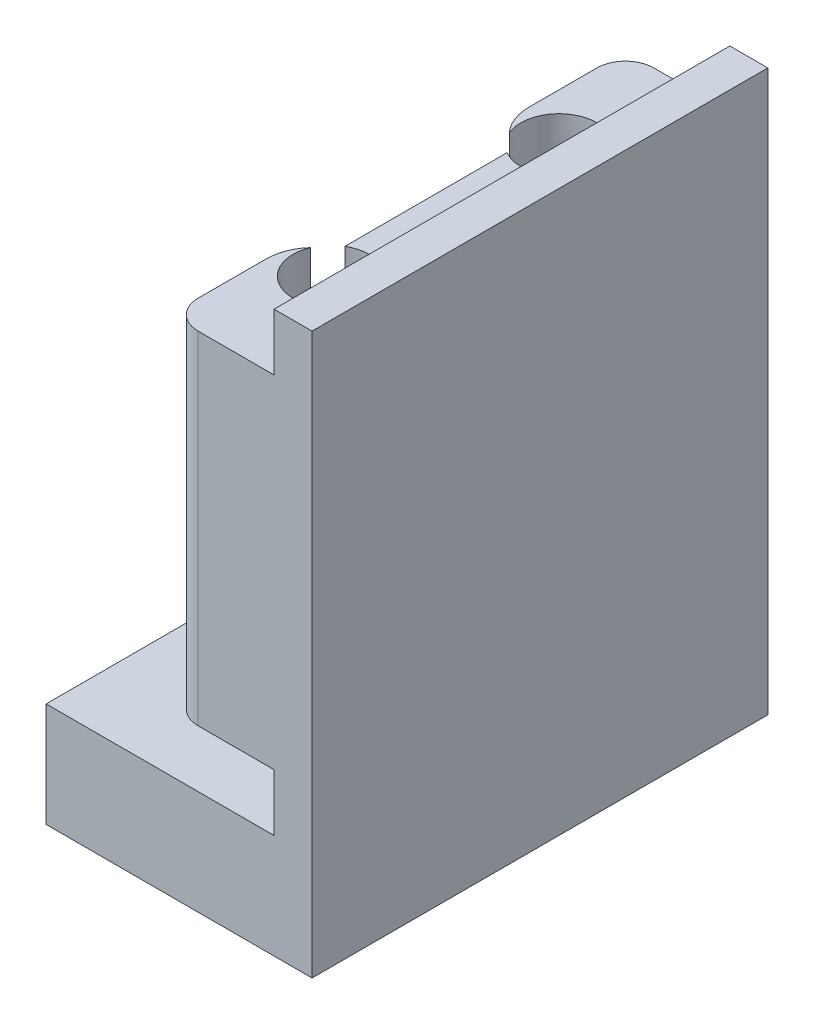
SolidWorks part; units mm, degrees
ref_plane "Front" through (0, 0, 0) normal (0, 0, 1) x (1, 0, 0)
ref_plane "Top" through (0, 0, 0) normal (0, 1, 0) x (1, 0, 0)
ref_plane "Right" through (0, 0, 0) normal (1, 0, 0) x (0, 0, -1)
sketch "Sketch1" plane through (0, 0, 0) normal (0, 1, 0) x (1, 0, 0)
  line L5 (-6, -12) -> (6, -12)
  line L6 (-6, -12) -> (-6, 12)
  line L7 (-6, 12) -> (6, 12)
  line L8 (6, -12) -> (6, 12)
  line L9 (-6, -12) -> (6, 12) construction
  line L10 (-6, 12) -> (6, -12) construction
  point P0 (0, 0)
  dimension "D1" = 12
  dimension "D2" = 24
extrude "Boss-Extrude1" add sketch "Sketch1" along normal blind 5.5
sketch "Sketch2" plane through (0, 0, 0) normal (0, 1, 0) x (1, 0, 0)
  line L0 (6, 12) -> (-6, 12) construction
  line L1 (6, -12) -> (8, -12)
  line L2 (6, -12) -> (6, 12)
  line L3 (6, 12) -> (8, 12)
  line L4 (8, -12) -> (8, 12)
  dimension "D1" = 2
extrude "Boss-Extrude2" add sketch "Sketch2" along normal blind 29.5
sketch "Sketch4" plane through (0, 5.5, 0) normal (0, 1, 0) x (1, 0, 0)
  line L1 (6, -12) -> (0.5, -12)
  line L2 (6, -12) -> (6, 12)
  line L3 (6, 12) -> (0.5, 12)
  line L4 (0.5, -12) -> (0.5, 12)
  line L5 (6, 12) -> (-6, 12) construction
  dimension "D1" = 5.5
extrude "Boss-Extrude4" add sketch "Sketch4" along normal blind 18 from offset 3
sketch "Sketch5" plane through (0.5, 0, 0) normal (-1, 0, 0) x (0, 0, 1)
  line L0 (-12, 26.5) -> (12, 26.5) construction
  line L1 (-4.625, 26.5) -> (4.625, 26.5)
  line L2 (-4.625, 26.5) -> (-4.625, 8.5)
  line L3 (-4.625, 8.5) -> (4.625, 8.5)
  line L4 (4.625, 26.5) -> (4.625, 8.5)
  line L5 (-12, 8.5) -> (12, 8.5) construction
  line L8 (4.625, 26.5) -> (12, 26.5) construction
  line L9 (-4.625, 26.5) -> (-12, 26.5) construction
  dimension "D1" = 9.25
extrude "Cut-Extrude1" cut sketch "Sketch5" against normal blind 1.5
fillet "Fillet1" radius 2.5 2 edges at (0.5, 17.5, 4.625) (0.5, 17.5, -4.625)
sketch "Sketch6" plane through (0, 26.5, 0) normal (0, 1, 0) x (1, 0, 0)
  line L0 (6, 0) -> (2, 0) construction
  line L1 (6, -12) -> (6, 12) construction
  line L2 (2, -4.625) -> (2, 4.625) construction
  line L3 (3, -12) -> (3, -6) construction
  line L4 (0.5, -12) -> (6, -12) construction
  line L5 (3, -6) -> (6, -6) construction
  circle A0 centre (3, -6) radius 2
  circle A1 centre (3, 6) radius 2
  dimension "D3" = 4
  dimension "D1" = 6
  dimension "D2" = 3
extrude "Cut-Extrude2" cut sketch "Sketch6" against normal through all
fillet "Fillet2" radius 1.5 2 edges at (0.5, 17.5, -12) (0.5, 17.5, 12)
